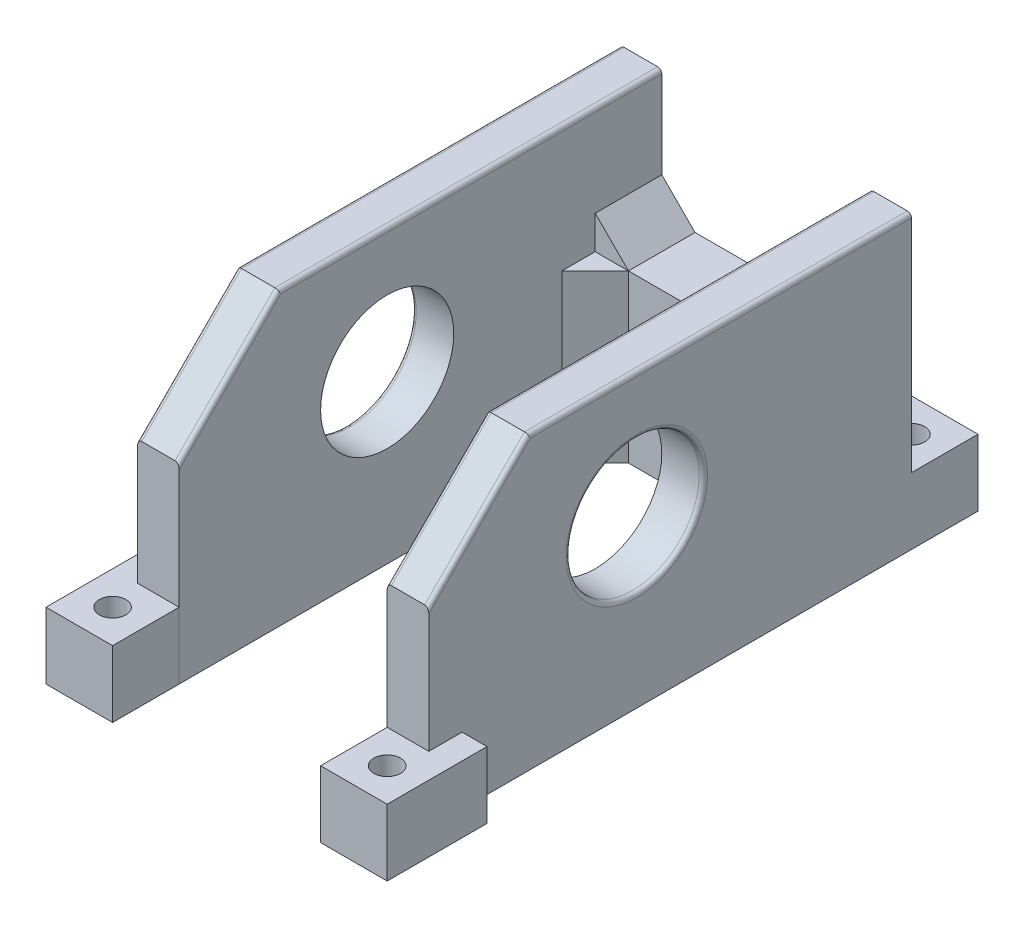
SolidWorks part; units mm, degrees
ref_plane "Plan de face" through (0, 0, 0) normal (0, 0, 1) x (1, 0, 0)
ref_plane "Plan de dessus" through (0, 0, 0) normal (0, 1, 0) x (1, 0, 0)
ref_plane "Plan de droite" through (0, 0, 0) normal (1, 0, 0) x (0, 0, -1)
sketch "Esquisse1" plane through (0, 0, 0) normal (0, 1, 0) x (1, 0, 0)
  line L4 (-18, -49) -> (-23, -49)
  line L5 (-23, -49) -> (-23, 9)
  line L8 (-18, 9) -> (-18, -49)
  line L9 (-18, 9) -> (7, 9)
  line L10 (-18, 1) -> (-14, 1) construction
  line L11 (-18, 1) -> (-18, -3) construction
  line L16 (-18, -3) -> (-14, 1)
  line L17 (-18, 9) -> (-23, 9)
  line L18 (7, 9) -> (7, -49)
  line L19 (7, 1) -> (3, 1) construction
  line L20 (-23, 9) -> (-23, 17)
  line L21 (-23, 17) -> (-15, 17)
  line L22 (-15, 17) -> (-15, 9)
  line L23 (7, -49) -> (12, -49)
  line L24 (12, -49) -> (12, 9)
  line L25 (12, 9) -> (7, 9)
  line L26 (-23, 17) -> (-15, 9) construction
  line L27 (-23, 9) -> (-15, 17) construction
  line L28 (3, 1) -> (-14, 1)
  line L29 (7, 1) -> (7, -3) construction
  line L30 (-18, -49) -> (-18, -57)
  line L31 (-18, -57) -> (-26, -57)
  line L32 (-26, -57) -> (-26, -45)
  line L33 (-26, -45) -> (-23, -45)
  line L34 (7, -3) -> (3, 1)
  line L35 (12, 9) -> (12, 17)
  line L36 (12, 17) -> (4, 17)
  line L37 (4, 17) -> (4, 9)
  line L38 (-23, -49) -> (-26, -49) construction
  line L39 (-26, -49) -> (-18, -57) construction
  line L40 (-26, -57) -> (-18, -49) construction
  line L41 (4, 9) -> (12, 17) construction
  line L42 (12, 9) -> (4, 17) construction
  line L43 (7, -49) -> (7, -57)
  line L44 (7, -57) -> (15, -57)
  line L45 (15, -57) -> (15, -45)
  line L46 (15, -45) -> (12, -45)
  line L47 (12, -49) -> (15, -49) construction
  line L48 (7, -49) -> (15, -57) construction
  line L49 (7, -57) -> (15, -49) construction
  circle A0 centre (-19, 13) radius 1.6
  circle A2 centre (-22, -53) radius 1.6
  circle A3 centre (8, 13) radius 1.6
  circle A4 centre (11, -53) radius 1.6
  dimension "D1" = 66
  dimension "D2" = 35
extrude "Boss.-Extru.1" add sketch "Esquisse1" along normal blind 35 contours L5 L4 | L18 L23 L24 L25 region at (-20.5, 0, 20)
sketch "Esquisse6" plane through (-23, 0, 0) normal (-1, 0, 0) x (0, 0, 1)
  line L0 (49, 0) -> (-1, 0) construction
  line L1 (49, 0) -> (-9, 0) construction
  line L2 (-1, 0) -> (-1, 35) construction
  line L3 (49, 35) -> (-9, 35) construction
  line L4 (-1, 35) -> (49, 35) construction
  line L5 (49, 35) -> (49, 0) construction
  line L6 (-1, 0) -> (49, 0)
  line L7 (24, 0) -> (24, 20) construction
  circle A0 centre (24, 20) radius 8
sketch "Esquisse7" plane through (-23, 0, 0) normal (-1, 0, 0) x (0, 0, 1)
  line L0 (49, 35) -> (49, 23)
  line L2 (49, 35) -> (49, 0) construction
  line L3 (49, 35) -> (37, 35)
  line L4 (-1, 35) -> (49, 35) construction
  line L5 (37, 35) -> (49, 23)
extrude "Boss.-Extru.6" add sketch "Esquisse1<5>" along normal blind 20 separate body contours L11 L16 L10 | L34 region at (-5.5, 0, -4.6049)
sketch "Esquisse1<5>" plane through (0, 0, 0) normal (0, 1, 0) x (1, 0, 0) same geometry as "Esquisse1"
extrude "Boss.-Extru.7" add sketch "Esquisse1<6>" along normal blind 8 contours L37 | L22 L21 L20 A0 region at (-20.5, 0, -9.1131) region at (4.1131, 0, -13)
sketch "Esquisse1<6>" plane through (0, 0, 0) normal (0, 1, 0) x (1, 0, 0) same geometry as "Esquisse1"
extrude "Boss.-Extru.8" add sketch "Esquisse1<8>" along normal blind 8 contours L33 L32 L31 L30 L4 L5 A2 | L44 region at (-18.1442, 0, 53) region at (9.5, 0, 49.1442)
sketch "Esquisse1<8>" plane through (0, 0, 0) normal (0, 1, 0) x (1, 0, 0) same geometry as "Esquisse1"
extrude "Enlèv. mat.-Extru.3" cut sketch "Esquisse7" against normal blind 40
extrude "Enlèv. mat.-Extru.4" cut sketch "Esquisse6" against normal blind 40 contours A0 region at (-23, 20, 24)
sketch "Esquisse10" plane through (0, 0, -9) normal (0, 0, -1) x (-1, 0, 0)
  line L0 (-7, 20) -> (-7, 24)
  line L1 (18, 20) -> (-7, 20) construction
  line L2 (-7, 35) -> (-7, 0) construction
  line L3 (-7, 20) -> (-3, 20)
  line L4 (-3, 20) -> (-7, 24)
  line L5 (18, 20) -> (14, 20)
  line L6 (18, 20) -> (18, 24)
  line L7 (18, 35) -> (18, 0) construction
  line L8 (18, 24) -> (14, 20)
extrude "Boss.-Extru.9" add sketch "Esquisse10" against normal blind 8
fillet "Congé1" radius 0.5 10 edges at (12, 20, 32) (-23, 20, 32) (-23, 29, 43) (-18, 29, 43) (7, 29, 43) (12, 29, 43) (-23, 35, 14) (-18, 35, 14) (7, 35, 14) (12, 35, 14)
sketch "Esquisse11" plane through (-23, 0, 0) normal (-1, 0, 0) x (0, 0, 1)
  line L0 (24, 20) -> (24, 0)
  line L1 (49, 0) -> (-17, 0) construction
  line L2 (24, 0) -> (49, 0)
  line L3 (24, 0) -> (-17, 0)
  dimension "D1" = 41
  dimension "D2" = 25
  dimension "D3" = 20
